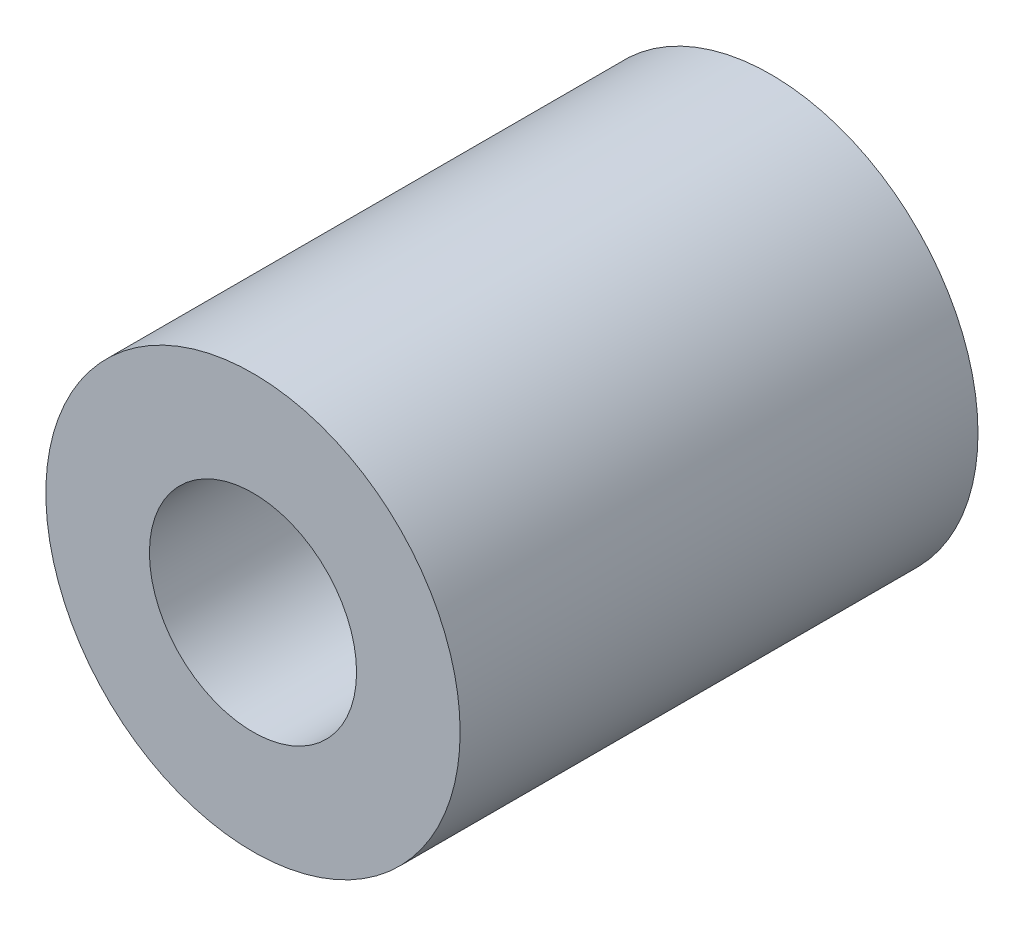
SolidWorks part; units mm, degrees
ref_plane "前视基准面" through (0, 0, 0) normal (0, 0, 1) x (1, 0, 0)
ref_plane "上视基准面" through (0, 0, 0) normal (0, 1, 0) x (1, 0, 0)
ref_plane "右视基准面" through (0, 0, 0) normal (1, 0, 0) x (0, 0, -1)
ref_axis "x轴" through (88.99, 0, 0) along (-1, 0, 0)
ref_axis "y轴" through (0, 0, -88.99) along (0, 0, 1)
ref_axis "z轴" through (0, -44, 0) along (0, 1, 0)
sketch "草图1" plane through (0, 0, 0) normal (0, 0, 1) x (1, 0, 0)
  circle A0 centre (0, 0) radius 10
  circle A1 centre (0, 0) radius 4
extrude "凸台-拉伸1" add sketch "草图1" along normal blind 25
sketch "草图2" plane through (0, 0, 25) normal (0, 0, 1) x (1, 0, 0)
  circle A0 centre (0, 0) radius 5
extrude "切除-拉伸1" cut sketch "草图2" against normal blind 12.5
